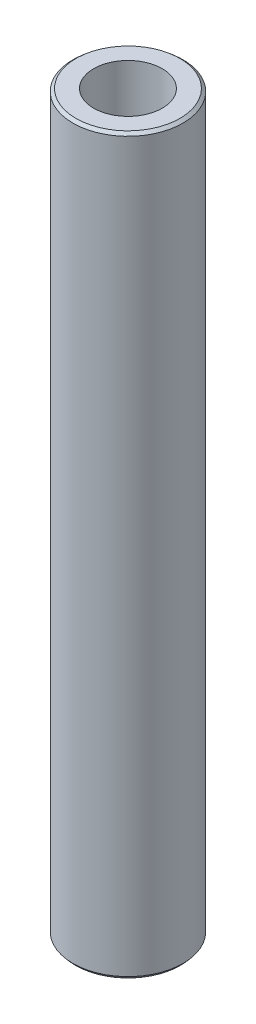
SolidWorks part; units mm, degrees
ref_plane "Front Plane" through (0, 0, 0) normal (0, 0, 1) x (1, 0, 0)
ref_plane "Top Plane" through (0, 0, 0) normal (0, 1, 0) x (1, 0, 0)
ref_plane "Right Plane" through (0, 0, 0) normal (1, 0, 0) x (0, 0, -1)
sketch "Sketch1" plane through (0, 0, 0) normal (0, 1, 0) x (1, 0, 0)
  circle A0 centre (0, 0) radius 45
  dimension "SHAFT_OD" = 90
extrude "Boss-Extrude1" add sketch "Sketch1" along normal blind 600
sketch "Sketch2" plane through (0, 0, 0) normal (0, 1, 0) x (1, 0, 0)
  circle A0 centre (0, 0) radius 28.0528
  dimension "BORE_D" = 56.1056
extrude "Cut-Extrude1" cut sketch "Sketch2" along normal through all
chamfer "Chamfer1" distance 2.1149 angle 49.608 2 edges at (0, 600, 45) (0, 0, 45) first distance on face at (0, 600, 45) first distance on face at (0, 0, 28.0528)
